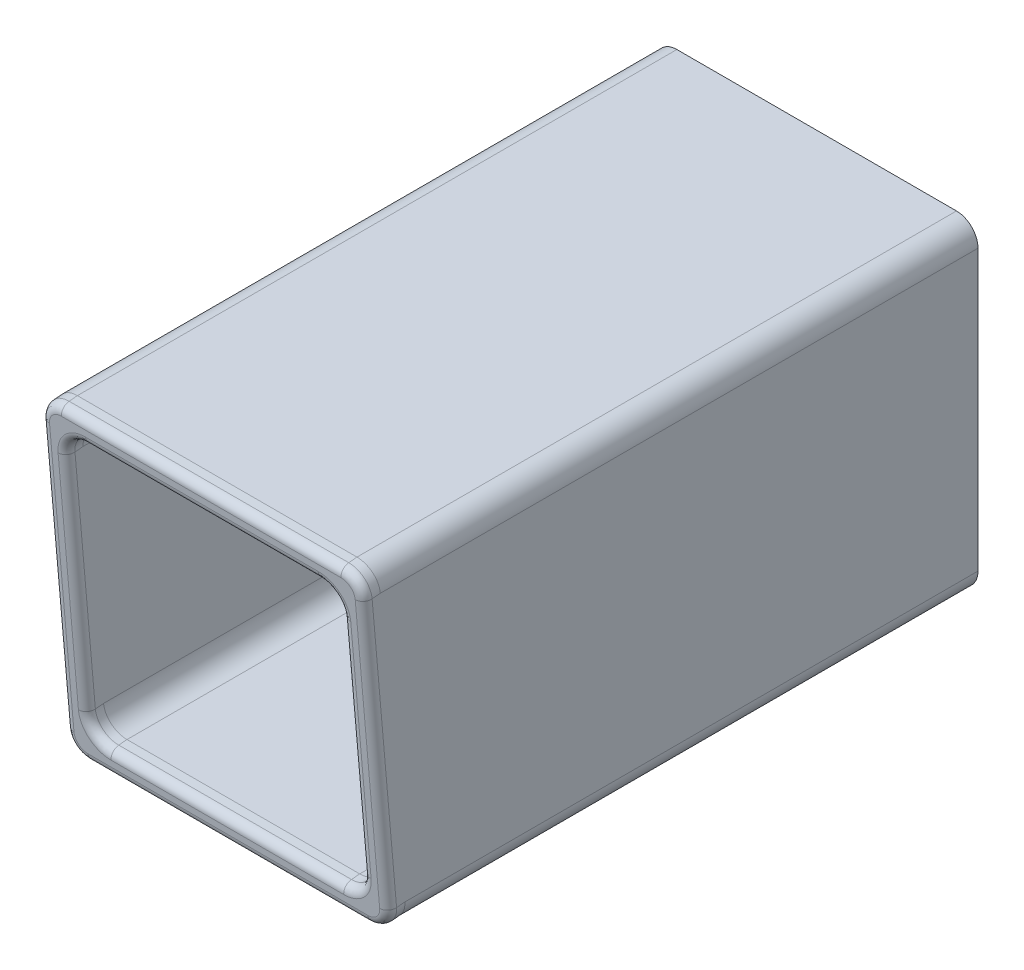
SolidWorks part; units mm, degrees
material "ASTM A500 Grade B Steel"
ref_plane "Front Plane" through (0, 0, 0) normal (0, 0, 1) x (1, 0, 0)
ref_plane "Top Plane" through (0, 0, 0) normal (0, 1, 0) x (1, 0, 0)
ref_plane "Right Plane" through (0, 0, 0) normal (1, 0, 0) x (0, 0, -1)
sketch "Sketch1" plane through (0, 0, 0) normal (0, 0, 1) x (1, 0, 0)
  line L0 (5.3086, -2.7686) -> (32.7914, -2.7686)
  line L1 (2.54, 0) -> (35.56, 0)
  line L2 (0, -2.54) -> (0, -35.56)
  line L3 (2.54, -38.1) -> (35.56, -38.1)
  line L4 (38.1, -2.54) -> (38.1, -35.56)
  line L5 (35.3314, -5.3086) -> (35.3314, -32.7914)
  line L6 (5.3086, -35.3314) -> (32.7914, -35.3314)
  line L7 (2.7686, -5.3086) -> (2.7686, -32.7914)
  line L8 (0, 0) -> (0, -38.1) construction
  line L9 (0, -38.1) -> (38.1, -38.1) construction
  line L10 (38.1, 0) -> (38.1, -38.1) construction
  line L11 (2.7686, -2.7686) -> (2.7686, -35.3314) construction
  line L12 (2.7686, -35.3314) -> (35.3314, -35.3314) construction
  line L13 (35.3314, -2.7686) -> (35.3314, -35.3314) construction
  line L14 (2.7686, -2.7686) -> (35.3314, -2.7686) construction
  line L15 (0, 0) -> (38.1, 0) construction
  arc A0 (0, -35.56) -> (2.54, -38.1) centre (2.54, -35.56) ccw
  arc A1 (38.1, -35.56) -> (35.56, -38.1) centre (35.56, -35.56) cw
  arc A2 (2.7686, -32.7914) -> (5.3086, -35.3314) centre (5.3086, -32.7914) ccw
  arc A3 (32.7914, -35.3314) -> (35.3314, -32.7914) centre (32.7914, -32.7914) ccw
  arc A4 (35.3314, -5.3086) -> (32.7914, -2.7686) centre (32.7914, -5.3086) ccw
  arc A5 (38.1, -2.54) -> (35.56, 0) centre (35.56, -2.54) ccw
  arc A6 (0, -2.54) -> (2.54, 0) centre (2.54, -2.54) cw
  arc A7 (5.3086, -2.7686) -> (2.7686, -5.3086) centre (5.3086, -5.3086) ccw
  point P12 (0, -38.1)
  dimension "D4" = 2.54
  dimension "D3" = 2.7686
extrude "Boss-Extrude1" add sketch "Sketch1" along normal blind 70.8
sketch "Sketch2" plane through (38.1, 0, 0) normal (1, 0, 0) x (0, 0, -1)
  line L0 (-70.8, 0) -> (-67.4667, -38.1)
  line L1 (-70.8, -38.1) -> (0, -38.1) construction
  line L2 (-67.4667, -38.1) -> (-70.8, -38.1)
  line L3 (-70.8, -38.1) -> (-70.8, 0)
  dimension "D1" = 5
extrude "Cut-Extrude1" cut sketch "Sketch2" against normal through all
sketch "Sketch3" plane through (0, -6.1471, 70.2622) normal (0, -0.0872, 0.9962) x (1, 0, 0)
  line L0 (35.3314, 0.8417) -> (35.3314, -26.746) construction
  line L1 (32.7914, -29.2957) -> (5.3086, -29.2957) construction
  line L2 (2.7686, -26.746) -> (2.7686, 0.8417) construction
  line L3 (5.3086, 3.3915) -> (32.7914, 3.3915) construction
  line L4 (2.54, -32.0749) -> (35.56, -32.0749)
  line L5 (38.1, -29.5252) -> (38.1, 3.6209)
  line L6 (35.56, 6.1706) -> (2.54, 6.1706)
  line L7 (0, 3.6209) -> (0, -29.5252)
  line L8 (2.54, -32.0749) -> (35.56, -32.0749)
  line L9 (38.1, -29.5252) -> (38.1, 3.6209)
  line L10 (35.56, 6.1706) -> (2.54, 6.1706)
  line L11 (0, 3.6209) -> (0, -29.5252)
  line L12 (35.3314, 0.8417) -> (35.3314, -26.746)
  line L13 (32.7914, -29.2957) -> (5.3086, -29.2957)
  line L14 (2.7686, -26.746) -> (2.7686, 0.8417)
  line L15 (5.3086, 3.3915) -> (32.7914, 3.3915)
  ellipse E0 centre (32.7914, 0.8417) end of major axis (32.7914, -1.708) minor radius 2.54 (35.3314, 0.8417) -> (32.7914, 3.3915) ccw construction
  ellipse E1 centre (32.7914, -26.746) end of major axis (32.7914, -29.2957) minor radius 2.54 (32.7914, -29.2957) -> (35.3314, -26.746) ccw construction
  ellipse E2 centre (5.3086, -26.746) end of major axis (5.3086, -29.2957) minor radius 2.54 (2.7686, -26.746) -> (5.3086, -29.2957) ccw construction
  ellipse E3 centre (5.3086, 0.8417) end of major axis (5.3086, -1.708) minor radius 2.54 (5.3086, 3.3915) -> (2.7686, 0.8417) ccw construction
  ellipse E4 centre (35.56, -29.5252) end of major axis (35.56, -32.0749) minor radius 2.54 (35.56, -32.0749) -> (38.1, -29.5252) ccw
  ellipse E5 centre (35.56, 3.6209) end of major axis (35.56, 1.0712) minor radius 2.54 (38.1, 3.6209) -> (35.56, 6.1706) ccw
  ellipse E6 centre (2.54, 3.6209) end of major axis (2.54, 1.0712) minor radius 2.54 (2.54, 6.1706) -> (0, 3.6209) ccw
  ellipse E7 centre (2.54, -29.5252) end of major axis (2.54, -32.0749) minor radius 2.54 (0, -29.5252) -> (2.54, -32.0749) ccw
  ellipse E8 centre (35.56, -29.5252) end of major axis (35.56, -32.0749) minor radius 2.54 (35.56, -32.0749) -> (38.1, -29.5252) ccw
  ellipse E9 centre (35.56, 3.6209) end of major axis (35.56, 1.0712) minor radius 2.54 (38.1, 3.6209) -> (35.56, 6.1706) ccw
  ellipse E10 centre (2.54, 3.6209) end of major axis (2.54, 1.0712) minor radius 2.54 (2.54, 6.1706) -> (0, 3.6209) ccw
  ellipse E11 centre (2.54, -29.5252) end of major axis (2.54, -32.0749) minor radius 2.54 (0, -29.5252) -> (2.54, -32.0749) ccw
  ellipse E12 centre (32.7914, 0.8417) end of major axis (32.7914, -1.708) minor radius 2.54 (35.3314, 0.8417) -> (32.7914, 3.3915) ccw
  ellipse E13 centre (32.7914, -26.746) end of major axis (32.7914, -29.2957) minor radius 2.54 (32.7914, -29.2957) -> (35.3314, -26.746) ccw
  ellipse E14 centre (5.3086, -26.746) end of major axis (5.3086, -29.2957) minor radius 2.54 (2.7686, -26.746) -> (5.3086, -29.2957) ccw
  ellipse E15 centre (5.3086, 0.8417) end of major axis (5.3086, -1.708) minor radius 2.54 (5.3086, 3.3915) -> (2.7686, 0.8417) ccw
  dimension "D1" = 0
extrude "Boss-Extrude2" add sketch "Sketch3" along normal up to surface (1.9765 mm away)
fillet "Fillet1" radius 1 16 edges at (0.7439, -0.9162, 72.7038) (19.05, -0.1723, 72.7689) (37.3561, -0.9162, 72.7038) (38.1, -19.2223, 71.1023) (37.3561, -37.5283, 69.5007) (19.05, -38.2723, 69.4356) (0.7439, -37.5283, 69.5007) (0, -19.2223, 71.1023) (19.05, -2.9409, 72.5267) (3.5125, -3.6848, 72.4616) (2.7686, -19.2223, 71.1023) (3.5125, -34.7597, 69.7429) (19.05, -35.5037, 69.6778) (34.5875, -34.7597, 69.7429) (35.3314, -19.2223, 71.1023) (34.5875, -3.6848, 72.4616)
